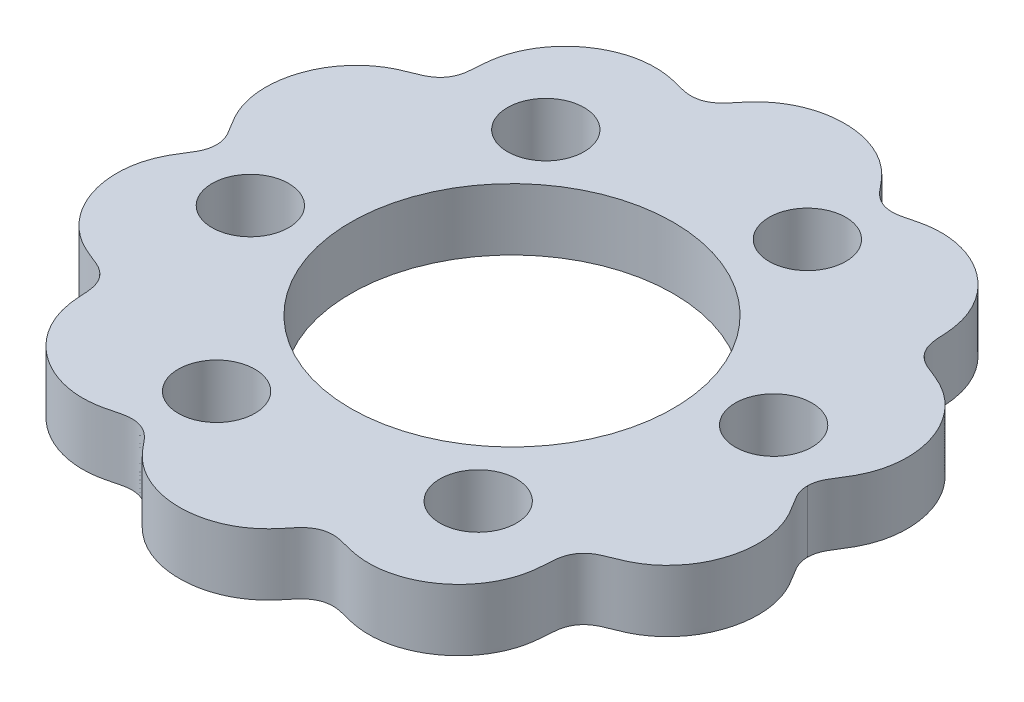
SolidWorks part; units mm, degrees
ref_plane "Front Plane" through (0, 0, 0) normal (0, 0, 1) x (1, 0, 0)
ref_plane "Top Plane" through (0, 0, 0) normal (0, 1, 0) x (1, 0, 0)
ref_plane "Right Plane" through (0, 0, 0) normal (1, 0, 0) x (0, 0, -1)
sketch "Sketch1" plane through (0, 0, 0) normal (0, 1, 0) x (1, 0, 0)
  spline S0 degree 4 poles (25.7906, 7.5343) (25.8788, 7.1133) (25.9899, 6.258) (25.9622, 5.173) (25.6669, 3.909) (25.2966, 3.0278) (25.0022, 2.4855) (24.7411, 2.0653) (24.5631, 1.7918) (24.4128, 1.5559) (24.2753, 1.3229) (24.1728, 1.1289) (24.0852, 0.9325) (24.0168, 0.7401) (23.9736, 0.5903) (23.9409, 0.4443) (23.918, 0.3017) (23.9061, 0.188) (23.9012, 0.082) (23.8998, 0.0096) (23.9001, -0.0378) (23.9031, -0.1354) (23.9124, -0.2583) (23.931, -0.3897) (23.9595, -0.5322) (23.992, -0.6548) (24.033, -0.7865) (24.0838, -0.9249) (24.1521, -1.083) (24.2429, -1.2629) (24.3447, -1.4425) (24.4552, -1.6225) (24.5717, -1.8045) (24.7183, -2.0313) (24.8914, -2.3053) (25.0875, -2.6402) (25.2934, -3.0428) (25.5234, -3.5754) (25.7435, -4.2491) (25.909, -5.0602) (25.989, -6.24) (25.8643, -7.4222) (25.5418, -8.5683) (25.0323, -9.6423) (24.5159, -10.4451) (23.8988, -11.1736) (23.1893, -11.8124) (22.5069, -12.2735) (21.8941, -12.5927) (21.3804, -12.8129) (20.9812, -12.967) (20.5083, -13.1497) (20.0028, -13.3924) (19.5163, -13.7704) (19.1071, -14.3429) (18.9044, -14.9387) (18.8377, -15.5108) (18.8117, -16.0408) (18.7845, -16.4899) (18.7247, -17.0578) (18.5966, -17.7393) (18.287, -18.7429) (17.6345, -19.995) (16.5677, -21.2689) (15.0187, -22.3804) (13.232, -23.0712) (11.6863, -23.2335) (10.5209, -23.1072) (9.745, -22.9271) (9.3314, -22.8175) (8.8415, -22.6876) (8.2891, -22.5904) (7.675, -22.6156) (7.014, -22.8425) (6.5078, -23.2036) (6.1238, -23.6204) (5.7973, -24.0261) (5.517, -24.3664) (4.9887, -24.958) (4.1217, -25.7163) (2.8002, -26.4589) (0.9866, -26.9323) (-0.8925, -26.9446) (-2.4927, -26.549) (-3.7586, -25.9235) (-4.6012, -25.2962) (-5.1069, -24.8217) (-5.4903, -24.3984) (-5.7768, -24.0514) (-6.1092, -23.6377) (-6.4971, -23.212) (-7.008, -22.8447) (-7.6734, -22.6157) (-8.2891, -22.5904) (-8.8414, -22.6876) (-9.3314, -22.8175) (-9.745, -22.9271) (-10.5209, -23.1072) (-11.6863, -23.2335) (-13.232, -23.0712) (-15.0187, -22.3804) (-16.5677, -21.2689) (-17.6345, -19.995) (-18.287, -18.7429) (-18.5966, -17.7393) (-18.7247, -17.0578) (-18.7845, -16.4899) (-18.8117, -16.0408) (-18.8377, -15.5108) (-18.9044, -14.9387) (-19.1071, -14.3429) (-19.5163, -13.7704) (-20.0028, -13.3924) (-20.5083, -13.1497) (-20.9812, -12.967) (-21.3804, -12.8129) (-21.8941, -12.5927) (-22.5069, -12.2735) (-23.1893, -11.8124) (-23.8988, -11.1736) (-24.5159, -10.4451) (-25.0323, -9.6423) (-25.5418, -8.5683) (-25.8643, -7.4222) (-25.989, -6.24) (-25.909, -5.0602) (-25.7435, -4.2491) (-25.5234, -3.5754) (-25.2934, -3.0428) (-25.0875, -2.6402) (-24.8914, -2.3053) (-24.7183, -2.0313) (-24.5717, -1.8045) (-24.4552, -1.6225) (-24.3447, -1.4425) (-24.2429, -1.2629) (-24.1521, -1.083) (-24.0838, -0.9249) (-24.033, -0.7865) (-23.992, -0.6548) (-23.9595, -0.5322) (-23.931, -0.3897) (-23.9124, -0.2583) (-23.9031, -0.1354) (-23.9001, -0.0378) (-23.8998, 0.0096) (-23.9012, 0.082) (-23.9061, 0.188) (-23.918, 0.3017) (-23.9409, 0.4443) (-23.9736, 0.5903) (-24.0168, 0.7401) (-24.0852, 0.9325) (-24.1918, 1.1715) (-24.3429, 1.4455) (-24.5376, 1.7528) (-24.7411, 2.0653) (-25.0022, 2.4855) (-25.2966, 3.0278) (-25.6669, 3.909) (-25.9622, 5.173) (-25.9899, 6.258) (-25.8788, 7.1133) (-25.7906, 7.5343) knots 0 0 0 0 0 0.016557 0.033114 0.041392 0.04967 0.053259 0.056848 0.060437 0.062231 0.064026 0.067263 0.068881 0.0705 0.071881 0.073262 0.074643 0.076024 0.076447 0.07687 0.077627 0.078384 0.079897 0.081411 0.082924 0.083871 0.084817 0.08671 0.088602 0.090495 0.092574 0.094654 0.096734 0.098813 0.102972 0.107132 0.111671 0.11621 0.125289 0.134368 0.143447 0.161605 0.170766 0.179928 0.18909 0.198252 0.207413 0.216574 0.220692 0.22481 0.228927 0.233045 0.240218 0.246328 0.252328 0.259785 0.264113 0.268441 0.27277 0.277098 0.286094 0.29509 0.313082 0.331073 0.349394 0.367716 0.386036 0.390153 0.39427 0.398387 0.402504 0.409677 0.415786 0.421726 0.429063 0.433304 0.437545 0.441787 0.446028 0.463838 0.481648 0.499458 0.517452 0.535446 0.544443 0.55344 0.557769 0.562098 0.566426 0.570755 0.578213 0.584214 0.590323 0.597496 0.601613 0.60573 0.609847 0.613964 0.632284 0.650606 0.668927 0.686918 0.70491 0.713906 0.722902 0.72723 0.731559 0.735887 0.740215 0.747672 0.753672 0.759782 0.766955 0.771073 0.77519 0.779308 0.783426 0.792587 0.801748 0.81091 0.820072 0.829234 0.838395 0.856553 0.865632 0.874711 0.88379 0.888329 0.892868 0.897028 0.901187 0.903266 0.905346 0.907426 0.909505 0.911398 0.91329 0.915183 0.916129 0.917076 0.918589 0.920103 0.921616 0.922373 0.92313 0.923553 0.923976 0.925357 0.926738 0.928119 0.9295 0.931119 0.932737 0.935974 0.939563 0.943152 0.946741 0.95033 0.958608 0.966886 0.983443 1 1 1 1 1 construction
  spline S1 degree 4 poles (23.9, 0) (23.9, -0.0166) (23.9004, -0.0497) (23.9031, -0.1354) (23.9124, -0.2583) (23.931, -0.3897) (23.9595, -0.5322) (23.992, -0.6548) (24.033, -0.7865) (24.0838, -0.9249) (24.1521, -1.083) (24.2429, -1.2629) (24.3447, -1.4425) (24.4552, -1.6225) (24.5717, -1.8045) (24.7183, -2.0313) (24.8914, -2.3053) (25.0875, -2.6402) (25.2934, -3.0428) (25.5234, -3.5754) (25.7435, -4.2491) (25.909, -5.0602) (25.989, -6.24) (25.8643, -7.4222) (25.5418, -8.5683) (25.0323, -9.6423) (24.5159, -10.4451) (23.8988, -11.1736) (23.1893, -11.8124) (22.5069, -12.2735) (21.8941, -12.5927) (21.3804, -12.8129) (20.9812, -12.967) (20.5083, -13.1497) (20.0028, -13.3924) (19.5163, -13.7704) (19.1071, -14.3429) (18.9044, -14.9387) (18.8377, -15.5108) (18.8117, -16.0408) (18.7845, -16.4899) (18.7247, -17.0578) (18.5966, -17.7393) (18.287, -18.7429) (17.6345, -19.995) (16.5677, -21.2689) (15.0187, -22.3804) (13.232, -23.0712) (11.6863, -23.2335) (10.5209, -23.1072) (9.745, -22.9271) (9.3314, -22.8175) (8.8415, -22.6876) (8.2891, -22.5904) (7.675, -22.6156) (7.014, -22.8425) (6.5078, -23.2036) (6.1238, -23.6204) (5.7973, -24.0261) (5.517, -24.3664) (4.9887, -24.958) (4.1217, -25.7163) (2.8002, -26.4589) (0.9866, -26.9323) (-0.8925, -26.9446) (-2.4927, -26.549) (-3.7586, -25.9235) (-4.6012, -25.2962) (-5.1069, -24.8217) (-5.4903, -24.3984) (-5.7768, -24.0514) (-6.1092, -23.6377) (-6.4971, -23.212) (-7.008, -22.8447) (-7.6734, -22.6157) (-8.2891, -22.5904) (-8.8414, -22.6876) (-9.3314, -22.8175) (-9.745, -22.9271) (-10.5209, -23.1072) (-11.6863, -23.2335) (-13.232, -23.0712) (-15.0187, -22.3804) (-16.5677, -21.2689) (-17.6345, -19.995) (-18.287, -18.7429) (-18.5966, -17.7393) (-18.7247, -17.0578) (-18.7845, -16.4899) (-18.8117, -16.0408) (-18.8377, -15.5108) (-18.9044, -14.9387) (-19.1071, -14.3429) (-19.5163, -13.7704) (-20.0028, -13.3924) (-20.5083, -13.1497) (-20.9812, -12.967) (-21.3804, -12.8129) (-21.8941, -12.5927) (-22.5069, -12.2735) (-23.1893, -11.8124) (-23.8988, -11.1736) (-24.5159, -10.4451) (-25.0323, -9.6423) (-25.5418, -8.5683) (-25.8643, -7.4222) (-25.989, -6.24) (-25.909, -5.0602) (-25.7435, -4.2491) (-25.5234, -3.5754) (-25.2934, -3.0428) (-25.0875, -2.6402) (-24.8914, -2.3053) (-24.7183, -2.0313) (-24.5717, -1.8045) (-24.4552, -1.6225) (-24.3447, -1.4425) (-24.2429, -1.2629) (-24.1521, -1.083) (-24.0838, -0.9249) (-24.033, -0.7865) (-23.992, -0.6548) (-23.9595, -0.5322) (-23.931, -0.3897) (-23.9124, -0.2583) (-23.9031, -0.1354) (-23.9004, -0.0497) (-23.9, -0.0166) (-23.9, 0) knots 0.07687 0.07687 0.07687 0.07687 0.07687 0.077627 0.078384 0.079897 0.081411 0.082924 0.083871 0.084817 0.08671 0.088602 0.090495 0.092574 0.094654 0.096734 0.098813 0.102972 0.107132 0.111671 0.11621 0.125289 0.134368 0.143447 0.161605 0.170766 0.179928 0.18909 0.198252 0.207413 0.216574 0.220692 0.22481 0.228927 0.233045 0.240218 0.246328 0.252328 0.259785 0.264113 0.268441 0.27277 0.277098 0.286094 0.29509 0.313082 0.331073 0.349394 0.367716 0.386036 0.390153 0.39427 0.398387 0.402504 0.409677 0.415786 0.421726 0.429063 0.433304 0.437545 0.441787 0.446028 0.463838 0.481648 0.499458 0.517452 0.535446 0.544443 0.55344 0.557769 0.562098 0.566426 0.570755 0.578213 0.584214 0.590323 0.597496 0.601613 0.60573 0.609847 0.613964 0.632284 0.650606 0.668927 0.686918 0.70491 0.713906 0.722902 0.72723 0.731559 0.735887 0.740215 0.747672 0.753672 0.759782 0.766955 0.771073 0.77519 0.779308 0.783426 0.792587 0.801748 0.81091 0.820072 0.829234 0.838395 0.856553 0.865632 0.874711 0.88379 0.888329 0.892868 0.897028 0.901187 0.903266 0.905346 0.907426 0.909505 0.911398 0.91329 0.915183 0.916129 0.917076 0.918589 0.920103 0.921616 0.922373 0.92313 0.92313 0.92313 0.92313 0.92313
  spline S2 degree 4 poles (-25.7906, -7.5343) (-25.8788, -7.1133) (-25.9899, -6.258) (-25.9622, -5.173) (-25.6669, -3.909) (-25.2966, -3.0278) (-25.0022, -2.4855) (-24.7411, -2.0653) (-24.5631, -1.7918) (-24.4128, -1.5559) (-24.2753, -1.3229) (-24.1728, -1.1289) (-24.0852, -0.9325) (-24.0168, -0.7401) (-23.9736, -0.5903) (-23.9409, -0.4443) (-23.918, -0.3017) (-23.9061, -0.188) (-23.9012, -0.082) (-23.8998, -0.0096) (-23.9001, 0.0378) (-23.9031, 0.1354) (-23.9124, 0.2583) (-23.931, 0.3897) (-23.9595, 0.5322) (-23.992, 0.6548) (-24.033, 0.7865) (-24.0838, 0.9249) (-24.1521, 1.083) (-24.2429, 1.2629) (-24.3447, 1.4425) (-24.4552, 1.6225) (-24.5717, 1.8045) (-24.7183, 2.0313) (-24.8914, 2.3053) (-25.0875, 2.6402) (-25.2934, 3.0428) (-25.5234, 3.5754) (-25.7435, 4.2491) (-25.909, 5.0602) (-25.989, 6.24) (-25.8643, 7.4222) (-25.5418, 8.5683) (-25.0323, 9.6423) (-24.5159, 10.4451) (-23.8988, 11.1736) (-23.1893, 11.8124) (-22.5069, 12.2735) (-21.8941, 12.5927) (-21.3804, 12.8129) (-20.9812, 12.967) (-20.5083, 13.1497) (-20.0028, 13.3924) (-19.5163, 13.7704) (-19.1071, 14.3429) (-18.9044, 14.9387) (-18.8377, 15.5108) (-18.8117, 16.0408) (-18.7845, 16.4899) (-18.7247, 17.0578) (-18.5966, 17.7393) (-18.287, 18.7429) (-17.6345, 19.995) (-16.5677, 21.2689) (-15.0187, 22.3804) (-13.232, 23.0712) (-11.6863, 23.2335) (-10.5209, 23.1072) (-9.745, 22.9271) (-9.3314, 22.8175) (-8.8415, 22.6876) (-8.2891, 22.5904) (-7.675, 22.6156) (-7.014, 22.8425) (-6.5078, 23.2036) (-6.1238, 23.6204) (-5.7973, 24.0261) (-5.517, 24.3664) (-4.9887, 24.958) (-4.1217, 25.7163) (-2.8002, 26.4589) (-0.9866, 26.9323) (0.8925, 26.9446) (2.4927, 26.549) (3.7586, 25.9235) (4.6012, 25.2962) (5.1069, 24.8217) (5.4903, 24.3984) (5.7768, 24.0514) (6.1092, 23.6377) (6.4971, 23.212) (7.008, 22.8447) (7.6734, 22.6157) (8.2891, 22.5904) (8.8414, 22.6876) (9.3314, 22.8175) (9.745, 22.9271) (10.5209, 23.1072) (11.6863, 23.2335) (13.232, 23.0712) (15.0187, 22.3804) (16.5677, 21.2689) (17.6345, 19.995) (18.287, 18.7429) (18.5966, 17.7393) (18.7247, 17.0578) (18.7845, 16.4899) (18.8117, 16.0408) (18.8377, 15.5108) (18.9044, 14.9387) (19.1071, 14.3429) (19.5163, 13.7704) (20.0028, 13.3924) (20.5083, 13.1497) (20.9812, 12.967) (21.3804, 12.8129) (21.8941, 12.5927) (22.5069, 12.2735) (23.1893, 11.8124) (23.8988, 11.1736) (24.5159, 10.4451) (25.0323, 9.6423) (25.5418, 8.5683) (25.8643, 7.4222) (25.989, 6.24) (25.909, 5.0602) (25.7435, 4.2491) (25.5234, 3.5754) (25.2934, 3.0428) (25.0875, 2.6402) (24.8914, 2.3053) (24.7183, 2.0313) (24.5717, 1.8045) (24.4552, 1.6225) (24.3447, 1.4425) (24.2429, 1.2629) (24.1521, 1.083) (24.0838, 0.9249) (24.033, 0.7865) (23.992, 0.6547) (23.9595, 0.5322) (23.931, 0.3896) (23.9124, 0.2584) (23.9031, 0.135) (23.8997, 0.0263) (23.8998, -0.0438) (23.905, -0.1791) (23.918, -0.3009) (23.9409, -0.4447) (23.9736, -0.5901) (24.0168, -0.7402) (24.0852, -0.9325) (24.1918, -1.1716) (24.3429, -1.4455) (24.5376, -1.7528) (24.7411, -2.0653) (25.0022, -2.4855) (25.2966, -3.0278) (25.6669, -3.9091) (25.9622, -5.173) (25.9899, -6.258) (25.8788, -7.1133) (25.7906, -7.5343) knots 0 0 0 0 0 0.016557 0.033114 0.041392 0.04967 0.053259 0.056848 0.060437 0.062231 0.064026 0.067263 0.068881 0.0705 0.071881 0.073262 0.074643 0.076024 0.076447 0.07687 0.077627 0.078384 0.079897 0.081411 0.082924 0.083871 0.084817 0.08671 0.088602 0.090495 0.092574 0.094654 0.096734 0.098813 0.102972 0.107132 0.111671 0.11621 0.125289 0.134368 0.143447 0.161605 0.170766 0.179928 0.18909 0.198252 0.207413 0.216574 0.220692 0.22481 0.228927 0.233045 0.240218 0.246328 0.252328 0.259785 0.264113 0.268441 0.27277 0.277098 0.286094 0.29509 0.313082 0.331073 0.349394 0.367716 0.386036 0.390153 0.39427 0.398387 0.402504 0.409677 0.415786 0.421726 0.429063 0.433304 0.437545 0.441787 0.446028 0.463838 0.481648 0.499458 0.517452 0.535446 0.544443 0.55344 0.557769 0.562098 0.566426 0.570755 0.578213 0.584214 0.590323 0.597496 0.601613 0.60573 0.609847 0.613964 0.632284 0.650606 0.668927 0.686918 0.70491 0.713906 0.722902 0.72723 0.731559 0.735887 0.740215 0.747672 0.753672 0.759782 0.766955 0.771073 0.77519 0.779308 0.783426 0.792587 0.801748 0.81091 0.820072 0.829234 0.838395 0.856553 0.865632 0.874711 0.88379 0.888329 0.892868 0.897028 0.901187 0.903266 0.905346 0.907426 0.909505 0.911398 0.91329 0.915183 0.916129 0.917076 0.918589 0.920103 0.921616 0.922373 0.92313 0.923976 0.925357 0.926738 0.928119 0.9295 0.931119 0.932737 0.935974 0.939563 0.943152 0.946741 0.95033 0.958608 0.966886 0.983443 1 1 1 1 1 construction
  spline S3 degree 4 poles (-23.9, 0) (-23.9, 0.0166) (-23.9004, 0.0497) (-23.9031, 0.1354) (-23.9124, 0.2583) (-23.931, 0.3897) (-23.9595, 0.5322) (-23.992, 0.6548) (-24.033, 0.7865) (-24.0838, 0.9249) (-24.1521, 1.083) (-24.2429, 1.2629) (-24.3447, 1.4425) (-24.4552, 1.6225) (-24.5717, 1.8045) (-24.7183, 2.0313) (-24.8914, 2.3053) (-25.0875, 2.6402) (-25.2934, 3.0428) (-25.5234, 3.5754) (-25.7435, 4.2491) (-25.909, 5.0602) (-25.989, 6.24) (-25.8643, 7.4222) (-25.5418, 8.5683) (-25.0323, 9.6423) (-24.5159, 10.4451) (-23.8988, 11.1736) (-23.1893, 11.8124) (-22.5069, 12.2735) (-21.8941, 12.5927) (-21.3804, 12.8129) (-20.9812, 12.967) (-20.5083, 13.1497) (-20.0028, 13.3924) (-19.5163, 13.7704) (-19.1071, 14.3429) (-18.9044, 14.9387) (-18.8377, 15.5108) (-18.8117, 16.0408) (-18.7845, 16.4899) (-18.7247, 17.0578) (-18.5966, 17.7393) (-18.287, 18.7429) (-17.6345, 19.995) (-16.5677, 21.2689) (-15.0187, 22.3804) (-13.232, 23.0712) (-11.6863, 23.2335) (-10.5209, 23.1072) (-9.745, 22.9271) (-9.3314, 22.8175) (-8.8415, 22.6876) (-8.2891, 22.5904) (-7.675, 22.6156) (-7.014, 22.8425) (-6.5078, 23.2036) (-6.1238, 23.6204) (-5.7973, 24.0261) (-5.517, 24.3664) (-4.9887, 24.958) (-4.1217, 25.7163) (-2.8002, 26.4589) (-0.9866, 26.9323) (0.8925, 26.9446) (2.4927, 26.549) (3.7586, 25.9235) (4.6012, 25.2962) (5.1069, 24.8217) (5.4903, 24.3984) (5.7768, 24.0514) (6.1092, 23.6377) (6.4971, 23.212) (7.008, 22.8447) (7.6734, 22.6157) (8.2891, 22.5904) (8.8414, 22.6876) (9.3314, 22.8175) (9.745, 22.9271) (10.5209, 23.1072) (11.6863, 23.2335) (13.232, 23.0712) (15.0187, 22.3804) (16.5677, 21.2689) (17.6345, 19.995) (18.287, 18.7429) (18.5966, 17.7393) (18.7247, 17.0578) (18.7845, 16.4899) (18.8117, 16.0408) (18.8377, 15.5108) (18.9044, 14.9387) (19.1071, 14.3429) (19.5163, 13.7704) (20.0028, 13.3924) (20.5083, 13.1497) (20.9812, 12.967) (21.3804, 12.8129) (21.8941, 12.5927) (22.5069, 12.2735) (23.1893, 11.8124) (23.8988, 11.1736) (24.5159, 10.4451) (25.0323, 9.6423) (25.5418, 8.5683) (25.8643, 7.4222) (25.989, 6.24) (25.909, 5.0602) (25.7435, 4.2491) (25.5234, 3.5754) (25.2934, 3.0428) (25.0875, 2.6402) (24.8914, 2.3053) (24.7183, 2.0313) (24.5717, 1.8045) (24.4552, 1.6225) (24.3447, 1.4425) (24.2429, 1.2629) (24.1521, 1.083) (24.0838, 0.9249) (24.033, 0.7865) (23.992, 0.6547) (23.9595, 0.5322) (23.931, 0.3896) (23.9124, 0.2584) (23.9031, 0.135) (23.9004, 0.0501) (23.9, 0.0166) (23.9, 0) knots 0.07687 0.07687 0.07687 0.07687 0.07687 0.077627 0.078384 0.079897 0.081411 0.082924 0.083871 0.084817 0.08671 0.088602 0.090495 0.092574 0.094654 0.096734 0.098813 0.102972 0.107132 0.111671 0.11621 0.125289 0.134368 0.143447 0.161605 0.170766 0.179928 0.18909 0.198252 0.207413 0.216574 0.220692 0.22481 0.228927 0.233045 0.240218 0.246328 0.252328 0.259785 0.264113 0.268441 0.27277 0.277098 0.286094 0.29509 0.313082 0.331073 0.349394 0.367716 0.386036 0.390153 0.39427 0.398387 0.402504 0.409677 0.415786 0.421726 0.429063 0.433304 0.437545 0.441787 0.446028 0.463838 0.481648 0.499458 0.517452 0.535446 0.544443 0.55344 0.557769 0.562098 0.566426 0.570755 0.578213 0.584214 0.590323 0.597496 0.601613 0.60573 0.609847 0.613964 0.632284 0.650606 0.668927 0.686918 0.70491 0.713906 0.722902 0.72723 0.731559 0.735887 0.740215 0.747672 0.753672 0.759782 0.766955 0.771073 0.77519 0.779308 0.783426 0.792587 0.801748 0.81091 0.820072 0.829234 0.838395 0.856553 0.865632 0.874711 0.88379 0.888329 0.892868 0.897028 0.901187 0.903266 0.905346 0.907426 0.909505 0.911398 0.91329 0.915183 0.916129 0.917076 0.918589 0.920103 0.921616 0.922373 0.92313 0.92313 0.92313 0.92313 0.92313
  point P0 (-68.4012, 19.3448)
extrude "Boss-Extrude1" add sketch "Sketch1" along normal blind 5
sketch "Sketch2" plane through (0, 5, 0) normal (0, 1, 0) x (1, 0, 0)
  circle A0 centre (0, 0) radius 13.05
  dimension "D1" = 26.1
extrude "Cut-Extrude1" cut sketch "Sketch2" against normal through all
sketch "Sketch3" plane through (0, 5, 0) normal (0, 1, 0) x (1, 0, 0)
  line L0 (0, 0) -> (33.4644, 0) construction
  line L1 (-2.75, 0) -> (2.75, 0) construction
  line L2 (0, 0) -> (18.2722, 2.894) construction
  circle A0 centre (18.2722, 2.894) radius 3.1
  dimension "D3" = 6.2
  dimension "D1" = 9
  dimension "D2" = 18.5
extrude "Cut-Extrude2" cut sketch "Sketch3" against normal through all
pattern_circular "CirPattern1" count 6 over 360 about axis through (0, 5, 0) along (0, 1, 0) of "Cut-Extrude2"
equation "\"pin_circle_R\" = 27"
equation "\"ecc\" = 1.5"
equation "\"n_pins\" = 11"
equation "\"pin_d\" = 3"
equation "\"out_pin_R\" = 18.5"
equation "\"disc_clr\" = 0.1"
equation "\"seat_6803\" = 26.1"
equation "\"disc_t\" = 5"
equation "\"D1@Sketch2\"=\"seat_6803\""
equation "\"D2@Sketch3\"=\"out_pin_R\""
equation "\"D3@Sketch3\"=\"pin_d\" + 2*\"ecc\" + \"out_hole_clr\""
equation "\"out_hole_clr\" = 0.2"
